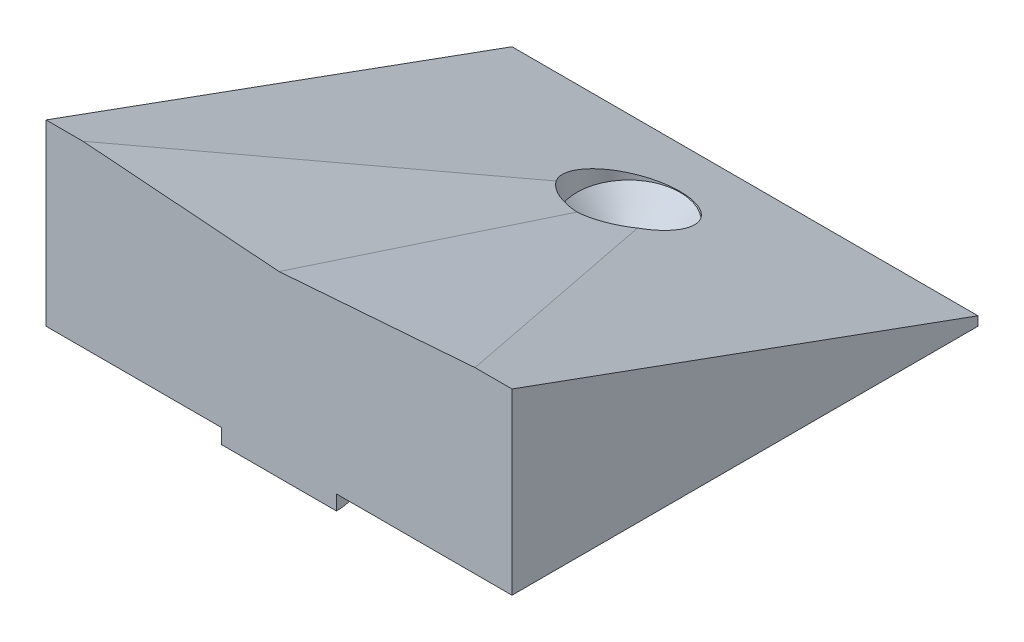
SolidWorks part; units mm, degrees
ref_plane "Front" through (0, 0, 0) normal (0, 0, 1) x (1, 0, 0)
ref_plane "Top" through (0, 0, 0) normal (0, 1, 0) x (1, 0, 0)
ref_plane "Right" through (0, 0, 0) normal (1, 0, 0) x (0, 0, -1)
ref_axis "side-side" through (80.9, 0, 0) along (-1, 0, 0)
ref_axis "up-down" through (0, 50, 0) along (0, -1, 0)
ref_axis "front-back" through (0, 0, -80.9) along (0, 0, 1)
sketch "Sketch2" plane through (0, 0, 0) normal (0, 1, 0) x (1, 0, 0)
  circle A1 centre (0, 8) radius 1.85
  circle A3 centre (0, 16) radius 4
  circle A5 centre (0, 24) radius 1.85
  circle A7 centre (-8, 16) radius 1.85
  circle A9 centre (8, 16) radius 1.85
  circle A11 centre (0, 0) radius 4
sketch "Sketch8" plane through (0, 0, 0) normal (1, 0, 0) x (0, 0, -1)
  line L0 (0, 50) -> (0, -50) construction
  line L2 (27.686, 2.1921) -> (32.004, 0.6204)
  dimension "D1" = 4.318
  dimension "D2" = 32.004
sketch "Sketch1" plane through (0, 0, 0) normal (1, 0, 0) x (0, 0, -1)
  line L0 (19.808, 5.0594) -> (19.808, 2.1921)
  line L1 (0, 0) -> (32, 0)
  line L2 (0, 0) -> (0, 12.269)
  line L3 (0, 12.269) -> (19.808, 5.0594)
  line L4 (32, 0) -> (32, 0.6219)
  line L5 (19.808, 2.1921) -> (27.686, 2.1921)
  line L6 (27.686, 2.1921) -> (32, 0.6219)
  dimension "D1" = 32
  dimension "D2" = 0.6219
  dimension "D3" = 20
  dimension "D4" = 2.1921
  dimension "D5" = 12.192
  dimension "D6" = 4.314
extrude "Boss-Extrude1" add sketch "Sketch1" along normal mid plane 32
hole_wizard "CSK for #6 Flat Head Machine Screw1" positions "Sketch4" profile "Sketch5" countersink size "#6" standard "ANSI Inch" end condition through all
sketch "Sketch4" plane through (0, 2.1921, 0) normal (0, 1, 0) x (1, 0, 0)
  point P0 (0, 24)
sketch "Sketch5" plane through (0, 2.1921, -24) normal (1, 0, 0) x (0, 0, 1)
  line L0 (0, 0) -> (0, 2.1921)
  line L1 (0, 2.1921) -> (1.8986, 2.1921)
  line L2 (1.8986, 2.1921) -> (1.8986, 1.892)
  line L3 (1.8986, 1.892) -> (3.5433, 0)
  line L5 (3.5433, 0) -> (0, 0)
  line L6 (-1.8986, 1.892) -> (-3.5433, 0) construction
  line L11 (0, -6.35) -> (0, 107.95) construction
  dimension "Thru Hole Dia." = 3.7973
  dimension "Thru Hole Depth" = 2.1921
  dimension "Near C'Sink Dia." = 7.0866
  dimension "Near C'Sink Angle" = 82
sketch "Sketch6" plane through (0, 2.1921, 0) normal (0, 1, 0) x (1, 0, 0)
  line L4 (-16, 27.686) -> (-16, 19.808)
  line L5 (-16, 19.808) -> (16, 19.808)
  line L6 (16, 19.808) -> (16, 27.686)
  line L7 (16, 27.686) -> (-16, 27.686)
  line L8 (-16, 27.686) -> (-16, 19.808)
  line L9 (-16, 19.808) -> (16, 19.808)
  line L10 (16, 19.808) -> (16, 27.686)
  line L11 (16, 27.686) -> (-16, 27.686)
  circle A0 centre (0, 24) radius 3.5433 construction
  circle A1 centre (0, 24) radius 3.5433
  dimension "D1" = 0
extrude "Boss-Extrude2" add sketch "Sketch6" along normal up to surface (2.8674 mm away) up to face at (0, 8.6642, -9.904)
sketch "Sketch7" plane through (0, 0, 0) normal (0, -1, 0) x (1, 0, 0)
  line L0 (16, 0) -> (-16, 0) construction
  line L1 (3.9492, 0) -> (-3.9492, 0)
  circle A2 centre (8, -16) radius 1.7992
  circle A3 centre (8, -16) radius 1.7992
  circle A5 centre (0, -16) radius 3.9492
  circle A6 centre (0, -16) radius 3.9492
  circle A8 centre (-8, -16) radius 1.7992
  circle A9 centre (-8, -16) radius 1.7992
  circle A11 centre (0, -8) radius 1.7992
  circle A12 centre (0, -8) radius 1.7992
  circle A14 centre (0, 0) radius 3.9492
  arc A15 (-3.9492, 0) -> (3.9492, 0) centre (0, 0) ccw
  dimension "D1" = 0.0508
  dimension "D2" = 0.0508
  dimension "D3" = 0.0508
  dimension "D4" = 0.0508
  dimension "D5" = 0.0508
extrude "Boss-Extrude3" add sketch "Sketch7" along normal blind 1.016
sketch "Sketch9" plane through (0, 0, 0) normal (0, 0, 1) x (1, 0, 0)
  line L0 (-13.46, 12.269) -> (0, 11.253)
  line L1 (16, 12.269) -> (-16, 12.269) construction
  line L2 (0, 11.253) -> (13.46, 12.269)
  line L3 (13.46, 12.269) -> (-13.46, 12.269)
  line L4 (-16, 12.269) -> (-16, 0) construction
  line L5 (16, 12.269) -> (16, 0) construction
  dimension "D1" = 2.54
  dimension "D2" = 2.54
  dimension "D3" = 1.016
sketch "Sketch10" plane through (0, 0, 0) normal (1, 0, 0) x (0, 0, -1)
  line L0 (0, 11.253) -> (27.5433, 2.244)
extrude "Cut-Extrude1" cut sketch "Sketch9" along direction (0, -0.3109, -0.9505) on the side against the normal through all
